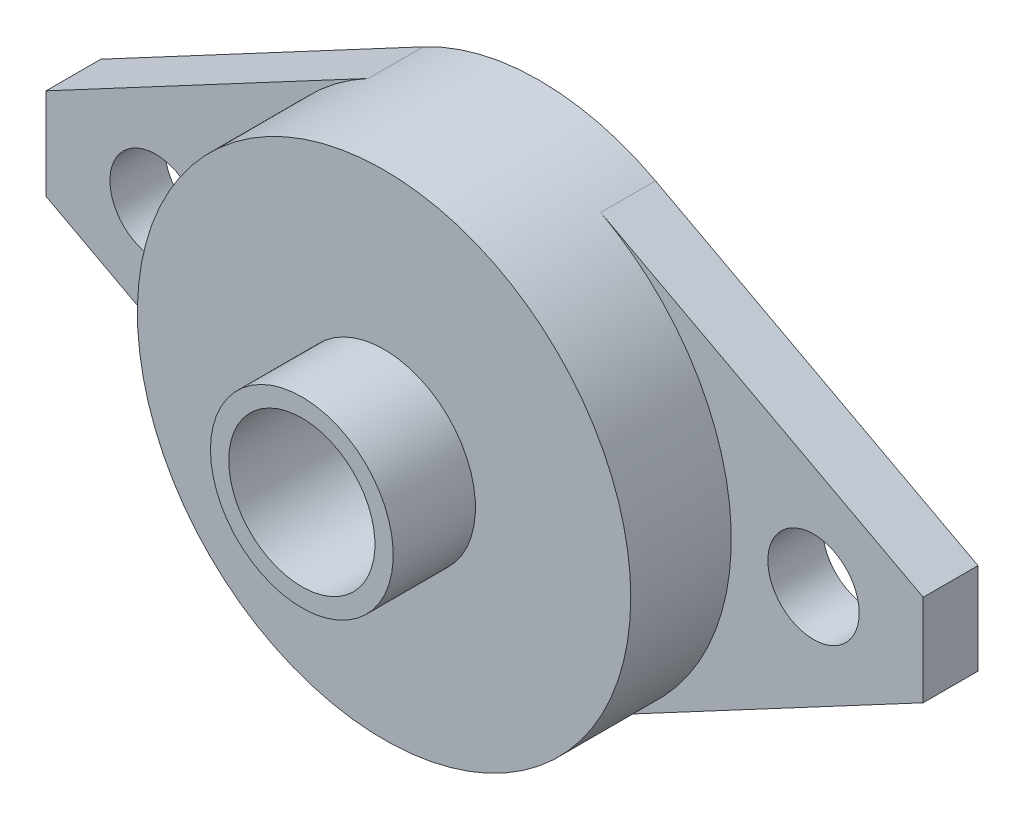
SolidWorks part; units mm, degrees
ref_plane "前视基准面" through (0, 0, 0) normal (0, 0, 1) x (1, 0, 0)
ref_plane "上视基准面" through (0, 0, 0) normal (0, 1, 0) x (1, 0, 0)
ref_plane "右视基准面" through (0, 0, 0) normal (1, 0, 0) x (0, 0, -1)
sketch "草图1" plane through (0, 0, 0) normal (0, 0, 1) x (1, 0, 0)
  line L0 (0, 26.6358) -> (0, 0) construction
  line L1 (0, 0) -> (40.3334, 0) construction
  line L2 (-24, -2.5) -> (-24, 2.5)
  line L3 (-24, 2.5) -> (-6.3529, 11.9118)
  line L4 (-24, -2.5) -> (-6.3529, -11.9118)
  line L5 (24, -2.5) -> (6.3529, -11.9118)
  line L6 (24, -2.5) -> (24, 2.5)
  line L7 (24, 2.5) -> (6.3529, 11.9118)
  circle A0 centre (-18, 0) radius 2.5
  circle A1 centre (0, 0) radius 5
  circle A2 centre (0, 0) radius 13.5
  circle A3 centre (0, 0) radius 4
  circle A4 centre (18, 0) radius 2.5
  point P13 (-24, 0)
  point P24 (-18, 2.5)
  dimension "D1" = 8
  dimension "D2" = 10
  dimension "D3" = 27
  dimension "D4" = 36
  dimension "D6" = 5
  dimension "D5" = 48
extrude "凸台-拉伸1" add sketch "草图1" along normal blind 3 contours A2 L3 L2 L4 A0 | A2 A1 | A2 L5 L6 L7 A4 region at (-23.7035, 0, 0) region at (-13.1182, 0, 0) region at (11.8304, -7.0982, 0)
extrude "凸台-拉伸2" add sketch "草图1<3>" along normal blind 8.5 contours A2 A1 region at (-13.1182, 0, 0)
sketch "草图1<3>" plane through (0, 0, 0) normal (0, 0, 1) x (1, 0, 0) same geometry as "草图1"
extrude "凸台-拉伸3" add sketch "草图1<4>" along normal blind 13 contours A1 A3 | A3 | A1 region at (-4.8586, 0, 0)
sketch "草图1<4>" plane through (0, 0, 0) normal (0, 0, 1) x (1, 0, 0) same geometry as "草图1"
